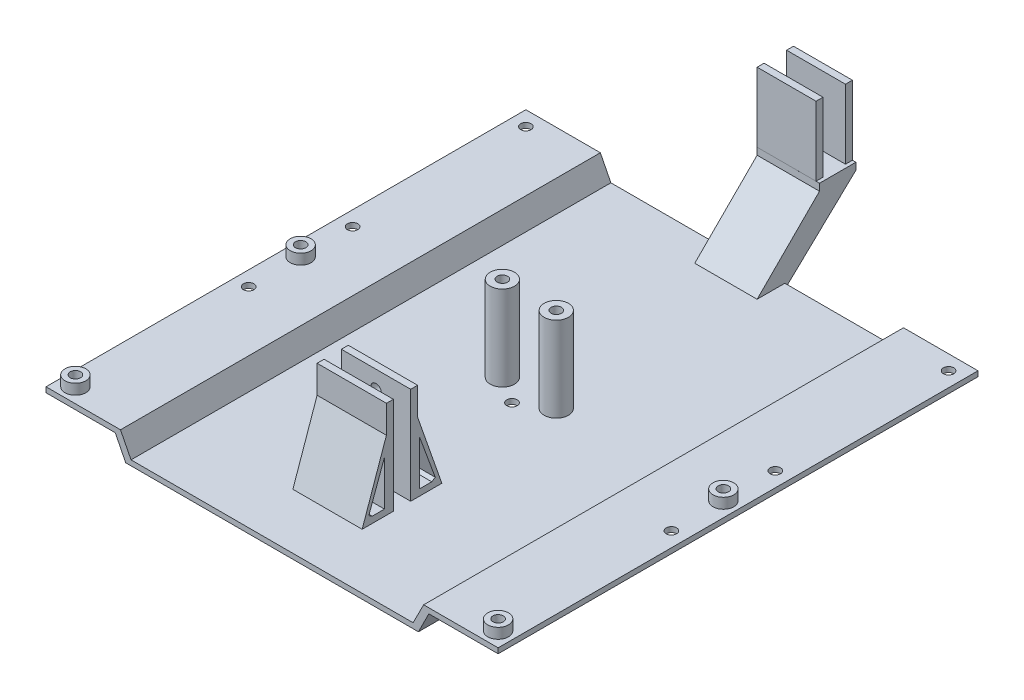
SolidWorks part; units mm, degrees
ref_plane "Front Plane" through (0, 0, 0) normal (0, 0, 1) x (1, 0, 0)
ref_plane "Top Plane" through (0, 0, 0) normal (0, 1, 0) x (1, 0, 0)
ref_plane "Right Plane" through (0, 0, 0) normal (1, 0, 0) x (0, 0, -1)
sketch "Sketch1" plane through (0, 0, 0) normal (0, 1, 0) x (1, 0, 0)
  line L0 (0, 0) -> (122, 0) construction
  line L1 (0, 0) -> (0, -130) construction
  line L2 (0, -130) -> (122, -130) construction
  line L3 (0, 0) -> (-4.2426, 4.2426) construction
  line L4 (122, -130) -> (126.2426, -134.2426) construction
  line L6 (-4.2426, 4.2426) -> (126.2426, 4.2426)
  line L7 (-4.2426, 4.2426) -> (-4.2426, -134.2426)
  line L8 (-4.2426, -134.2426) -> (126.2426, -134.2426)
  line L9 (126.2426, 4.2426) -> (126.2426, -134.2426)
  circle A0 centre (0, 0) radius 1.5
  circle A1 centre (122, 0) radius 1.5
  circle A2 centre (0, -130) radius 1.5
  circle A3 centre (122, -130) radius 1.5
  dimension "D1" = 122
  dimension "D2" = 130
  dimension "D3" = 6
extrude "Boss-Extrude1" add sketch "Sketch1" along normal blind 1.5 contours A3 | A2 | A0 | A1 | L7 L6 L9 L8 region at (0, 0, 0) region at (122, 0, 0) region at (0, 0, 130) region at (122, 0, 130)
sketch "Sketch3" plane through (0, 1.5, 0) normal (0, 1, 0) x (1, 0, 0)
  line L0 (-4.2426, -65) -> (15.7574, -65) construction
  line L1 (-4.2426, 4.2426) -> (-4.2426, -134.2426) construction
  line L2 (15.7574, -65) -> (15.7574, 4.2426)
  line L3 (-4.2426, 4.2426) -> (126.2426, 4.2426) construction
  line L4 (15.7574, -65) -> (15.7574, -134.2426)
  line L5 (-4.2426, -134.2426) -> (126.2426, -134.2426) construction
  line L6 (61, 4.2426) -> (61, -62.9629) construction
  line L7 (106.2426, -65) -> (106.2426, -134.2426)
  line L8 (106.2426, -65) -> (106.2426, 4.2426)
  line L9 (15.7574, 4.2426) -> (106.2426, 4.2426)
  line L10 (106.2426, -134.2426) -> (15.7574, -134.2426)
  dimension "D1" = 20
extrude "Cut-Extrude1" cut sketch "Sketch3" against normal blind 17.5
sketch "Sketch4" plane through (0, 0, 134.2426) normal (0, 0, 1) x (1, 0, 0)
  line L0 (15.7574, 0) -> (15.7574, -6) construction
  line L1 (15.7574, -6) -> (18.7574, -6) construction
  line L2 (15.7574, 0) -> (18.7574, -6)
  line L3 (15.7574, 0.75) -> (106.2426, 0.75) construction
  line L4 (15.7574, 0) -> (15.7574, 1.5) construction
  line L5 (106.2426, 0) -> (106.2426, 1.5) construction
  line L6 (61, 0.75) -> (61, -2.6317) construction
  line L7 (18.7574, -6) -> (103.2426, -6)
  line L8 (15.7574, 1.5) -> (17.2574, 1.5)
  line L9 (31.5588, -6) -> (31.5588, -4.5) construction
  line L10 (17.2574, 1.5) -> (20.2961, -4.5)
  line L11 (20.2961, -4.5) -> (38.3727, -4.5)
  line L12 (38.3727, -4.5) -> (83.6273, -4.5)
  line L13 (104.7426, 1.5) -> (101.7039, -4.5)
  line L14 (106.2426, 0) -> (103.2426, -6)
  line L15 (106.2426, 1.5) -> (104.7426, 1.5)
  line L16 (101.7039, -4.5) -> (83.6273, -4.5)
  line L17 (15.7574, 1.5) -> (15.7574, 0)
  line L18 (106.2426, 1.5) -> (106.2426, 0)
  point P18 (61, -6)
  point P27 (61, -4.5)
  dimension "D1" = 6
  dimension "D2" = 3
  dimension "D3" = 1.5
  dimension "D4" = 1.5
extrude "Boss-Extrude2" add sketch "Sketch4" against normal through all
sketch "Sketch14" plane through (0, 1.5, 0) normal (0, 1, 0) x (1, 0, 0)
  line L0 (61, -134.2426) -> (61, -121.7294) construction
  line L1 (101.7039, -134.2426) -> (20.2961, -134.2426) construction
  circle A0 centre (0, -130) radius 1.5
  circle A1 centre (0, -130) radius 3
  circle A2 centre (122, -130) radius 1.5
  circle A3 centre (122, -130) radius 3
extrude "Boss-Extrude7" add sketch "Sketch14" along normal blind 3
sketch "Sketch15" plane through (0, 1.5, 0) normal (0, 1, 0) x (1, 0, 0)
  line L0 (0, -130) -> (0, -65) construction
  line L1 (61, -134.2426) -> (61, -125.9107) construction
  line L2 (101.7039, -134.2426) -> (20.2961, -134.2426) construction
  circle A0 centre (0, -65) radius 1.5
  circle A1 centre (122, -65) radius 1.5
  dimension "D1" = 65
extrude "Cut-Extrude6" cut sketch "Sketch15" against normal blind 3
sketch "Sketch16" plane through (0, 1.5, 0) normal (0, 1, 0) x (1, 0, 0)
  line L0 (61, -134.2426) -> (61, -121.7051) construction
  line L1 (101.7039, -134.2426) -> (20.2961, -134.2426) construction
  circle A0 centre (0, -65) radius 3
  circle A1 centre (122, -65) radius 3
  circle A2 centre (0, -65) radius 1.5
  circle A3 centre (122, -65) radius 1.5
extrude "Boss-Extrude8" add sketch "Sketch16" along normal blind 3
sketch "Sketch17" plane through (0, 1.5, 0) normal (0, 1, 0) x (1, 0, 0)
  line L0 (0, -65) -> (0, -50) construction
  line L1 (0, -65) -> (6.6664, -65) construction
  line L2 (61, -134.2426) -> (61, -121.4665) construction
  line L3 (101.7039, -134.2426) -> (20.2961, -134.2426) construction
  circle A0 centre (0, -50) radius 1.5
  circle A1 centre (0, -80) radius 1.5
  circle A2 centre (122, -80) radius 1.5
  circle A3 centre (122, -50) radius 1.5
  dimension "D1" = 15
extrude "Cut-Extrude7" cut sketch "Sketch17" against normal blind 3
sketch "Sketch18" plane through (0, -4.5, 0) normal (0, 1, 0) x (1, 0, 0)
  line L0 (61, 4.2426) -> (61, -134.2426) construction
  line L1 (101.7039, 4.2426) -> (20.2961, 4.2426) construction
  line L2 (101.7039, -134.2426) -> (20.2961, -134.2426) construction
  line L3 (61, -65) -> (53.22, -65) construction
  line L4 (53.22, -65) -> (53.22, -60) construction
  circle A0 centre (53.22, -60) radius 1.5
  circle A1 centre (53.22, -60) radius 3.5
  circle A2 centre (68.78, -60) radius 3.5
  circle A3 centre (68.78, -60) radius 1.5
  dimension "D1" = 7.78
  dimension "D2" = 5
extrude "Boss-Extrude9" add sketch "Sketch18" along normal blind 24.5 contours A1 | A2 | A0 | A3
sketch "Sketch19" plane through (0, -4.5, 0) normal (0, 1, 0) x (1, 0, 0)
  line L0 (61, -134.2426) -> (61, -109.2426) construction
  line L1 (101.7039, -134.2426) -> (20.2961, -134.2426) construction
  line L2 (61, -109.2426) -> (51, -109.2426) construction
  line L3 (61, -109.2426) -> (71, -109.2426) construction
  line L4 (51, -109.2426) -> (51, -111.2426) construction
  line L5 (61, -109.2426) -> (61, -104.2426) construction
  line L6 (51, -111.2426) -> (71, -111.2426)
  line L7 (51, -111.2426) -> (51, -109.2426)
  line L8 (51, -109.2426) -> (71, -109.2426)
  line L9 (71, -111.2426) -> (71, -109.2426)
  line L10 (51, -104.2426) -> (61, -104.2426) construction
  line L11 (61, -104.2426) -> (71, -104.2426) construction
  line L12 (71, -104.2426) -> (71, -102.2426) construction
  line L14 (51, -104.2426) -> (71, -104.2426)
  line L15 (51, -104.2426) -> (51, -102.2426)
  line L16 (51, -102.2426) -> (71, -102.2426)
  line L17 (71, -104.2426) -> (71, -102.2426)
  dimension "D1" = 25
  dimension "D2" = 10
  dimension "D3" = 10
  dimension "D4" = 2
  dimension "D5" = 5
  dimension "D6" = 2
extrude "Boss-Extrude10" add sketch "Sketch19" along normal blind 28 contours L6 L9 L8 L7 | L15 L14 L17 L16 region at (61, -4.5, 110.2426)
sketch "Sketch20" plane through (71, 0, 0) normal (1, 0, 0) x (0, 0, -1)
  line L0 (-111.2426, -4.5) -> (-111.2426, 15.5) construction
  line L1 (-111.2426, 23.5) -> (-111.2426, -4.5) construction
  line L2 (-111.2426, -4.5) -> (-118.2426, -4.5)
  line L3 (-118.2426, -4.5) -> (-111.2426, 15.5)
  line L4 (-111.2426, 15.5) -> (-111.2426, -4.5)
  line L5 (-109.2426, -4.5) -> (-104.2426, -4.5) construction
  line L6 (-106.7426, -4.5) -> (-106.7426, 0) construction
  line L7 (-115.3294, -2.6686) -> (-111.8038, -2.6686)
  line L8 (-111.8038, -2.6686) -> (-111.8038, 10.2973)
  line L9 (-111.8038, 10.2973) -> (-116.3374, -2.0408)
  line L10 (-116.3374, -2.0408) -> (-115.3294, -2.6686)
  line L11 (-101.6815, 10.2973) -> (-97.1479, -2.0408)
  line L12 (-101.6815, -2.6686) -> (-101.6815, 10.2973)
  line L13 (-98.1559, -2.6686) -> (-101.6815, -2.6686)
  line L14 (-97.1479, -2.0408) -> (-98.1559, -2.6686)
  line L15 (-95.2426, -4.5) -> (-102.2426, 15.5)
  line L16 (-102.2426, -4.5) -> (-95.2426, -4.5)
  line L17 (-102.2426, 15.5) -> (-102.2426, -4.5)
  dimension "D1" = 20
  dimension "D2" = 7
extrude "Boss-Extrude11" add sketch "Sketch20" against normal blind 20
sketch "Sketch21" plane through (0, 0, 102.2426) normal (0, 0, -1) x (-1, 0, 0)
  line L0 (-61, 23.5) -> (-61, 15.5) construction
  line L1 (-51, 23.5) -> (-71, 23.5) construction
  line L2 (-51, 15.5) -> (-71, 15.5) construction
  circle A0 centre (-61, 18.456) radius 1.5
extrude "Cut-Extrude8" cut sketch "Sketch21" against normal blind 3
sketch "Sketch24" plane through (0, -4.5, 0) normal (0, 1, 0) x (1, 0, 0)
  line L0 (61, 4.2426) -> (61, -134.2426) construction
  line L1 (101.7039, 4.2426) -> (20.2961, 4.2426) construction
  line L2 (101.7039, -134.2426) -> (20.2961, -134.2426) construction
  circle A0 centre (61, -65) radius 1.5
extrude "Cut-Extrude9" cut sketch "Sketch24" against normal blind 16
sketch "Sketch26" plane through (0, 0, 102.2426) normal (0, 0, -1) x (-1, 0, 0)
  line L0 (-61, 18.456) -> (-61, 21.244) construction
  circle A0 centre (-61, 18.456) radius 3.0847
  circle A1 centre (-61, 18.456) radius 1.5
extrude "Boss-Extrude12" add sketch "Sketch26" along normal blind 2 contours A0 | A1
sketch "Sketch27" plane through (0, -4.5, 0) normal (0, 1, 0) x (1, 0, 0)
  line L0 (61, 4.2426) -> (61, 14.2426) construction
  line L1 (101.7039, 4.2426) -> (20.2961, 4.2426) construction
  line L2 (61, 14.2426) -> (52.5, 14.2426)
  line L3 (52.5, 14.2426) -> (52.5, 16.2426)
  line L4 (61, 14.2426) -> (69.5, 14.2426) construction
  line L5 (61, 16.2426) -> (61, 22.7426) construction
  line L6 (52.5, 16.2426) -> (69.5, 16.2426)
  line L7 (52.5, 16.2426) -> (52.5, 14.2426)
  line L8 (52.5, 14.2426) -> (69.5, 14.2426)
  line L9 (69.5, 16.2426) -> (69.5, 14.2426)
  line L10 (61, 22.7426) -> (52.5, 22.7426) construction
  line L11 (69.5, 14.2426) -> (69.5, 7.1661) construction
  line L12 (69.5, 7.1661) -> (69.5, 5.1661) construction
  line L18 (52.5, 22.7426) -> (69.5, 22.7426)
  line L19 (52.5, 22.7426) -> (52.5, 24.7426)
  line L20 (52.5, 24.7426) -> (69.5, 24.7426)
  line L21 (69.5, 22.7426) -> (69.5, 24.7426)
  dimension "D1" = 10
  dimension "D2" = 8.5
  dimension "D3" = 2
  dimension "D4" = 8.5
  dimension "D5" = 6.5
  dimension "D6" = 2
  dimension "D7" = 2
extrude "Boss-Extrude13" add sketch "Sketch27" along normal blind 40 separate body contours L9 L6 L3 L2 L8 | L19 L18 L21 L20 region at (61, -4.5, -15.2426)
sketch "Sketch28" plane through (0, -4.5, 0) normal (0, -1, 0) x (1, 0, 0)
  line L1 (46.1941, -10.7411) -> (75.7306, -10.7411)
  line L2 (46.1941, -10.7411) -> (46.1941, -26.5844)
  line L3 (46.1941, -26.5844) -> (75.7306, -26.5844)
  line L4 (75.7306, -10.7411) -> (75.7306, -26.5844)
extrude "Cut-Extrude10" cut sketch "Sketch28" against normal blind 20
sketch "Sketch29" plane through (52.5, 0, 0) normal (-1, 0, 0) x (0, 0, 1)
  line L0 (-24.7426, 13.5) -> (-4.2426, -6)
  line L1 (-24.7426, 15.5) -> (-14.2417, 15.5)
  line L2 (-24.7426, 15.5) -> (-24.7426, 13.5)
  line L4 (-14.2417, 15.5) -> (-14.2417, 13.5)
  line L5 (-14.2417, 13.5) -> (4.7384, -5.4801)
  line L6 (4.7384, -5.4801) -> (-4.2426, -6)
  dimension "D1" = 2
extrude "Boss-Extrude14" add sketch "Sketch29" against normal blind 18
